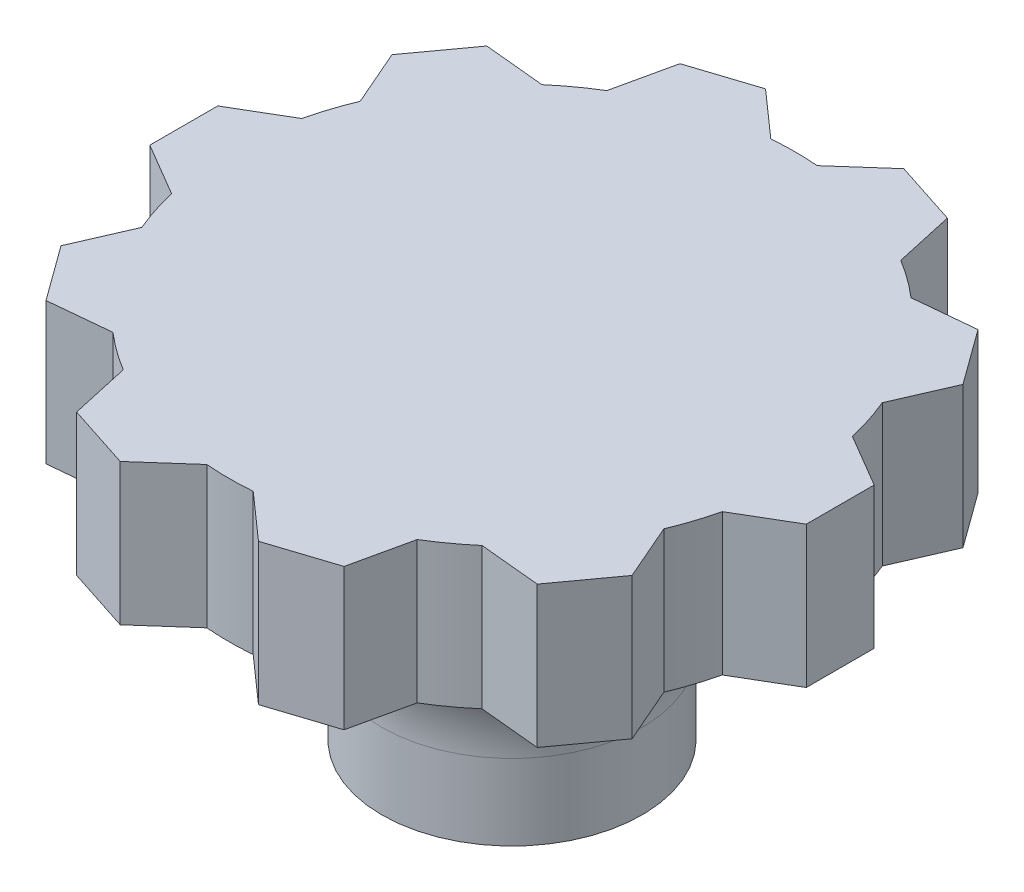
SolidWorks part; units mm, degrees
ref_plane "Front Plane" through (0, 0, 0) normal (0, 0, 1) x (1, 0, 0)
ref_plane "Top Plane" through (0, 0, 0) normal (0, 1, 0) x (1, 0, 0)
ref_plane "Right Plane" through (0, 0, 0) normal (1, 0, 0) x (0, 0, -1)
sketch "Sketch1" plane through (0, 0, 0) normal (0, 1, 0) x (1, 0, 0)
  circle A0 centre (0, 0) radius 11.5
extrude "Boss-Extrude1" add sketch "Sketch1" along normal blind 20
sketch "Sketch2" plane through (0, 20, 0) normal (0, 1, 0) x (1, 0, 0)
  line L1 (29, 0) -> (29, 3)
  line L2 (29, 0) -> (29, -3)
  line L5 (29, 3) -> (24.33, 5.7489)
  line L6 (29, -3) -> (24.33, -5.7489)
  line L9 (25.2248, -14.6187) -> (23.0625, -9.6498)
  line L10 (23.4615, -17.0458) -> (25.2248, -14.6187)
  line L11 (23.4615, -17.0458) -> (21.6981, -19.4728)
  line L12 (21.6981, -19.4728) -> (16.3043, -18.9518)
  line L15 (11.8147, -26.6536) -> (12.986, -21.3627)
  line L16 (8.9615, -27.5806) -> (11.8147, -26.6536)
  line L17 (8.9615, -27.5806) -> (6.1083, -28.5077)
  line L18 (6.1083, -28.5077) -> (2.0508, -24.9157)
  line L21 (-6.1083, -28.5077) -> (-2.0508, -24.9157)
  line L22 (-8.9615, -27.5806) -> (-6.1083, -28.5077)
  line L23 (-8.9615, -27.5806) -> (-11.8147, -26.6536)
  line L24 (-11.8147, -26.6536) -> (-12.986, -21.3627)
  line L27 (-21.6981, -19.4728) -> (-16.3043, -18.9518)
  line L28 (-23.4615, -17.0458) -> (-21.6981, -19.4728)
  line L29 (-23.4615, -17.0458) -> (-25.2248, -14.6187)
  line L30 (-25.2248, -14.6187) -> (-23.0625, -9.6498)
  line L33 (-29, -3) -> (-24.33, -5.7489)
  line L34 (-29, 0) -> (-29, -3)
  line L35 (-29, 0) -> (-29, 3)
  line L36 (-29, 3) -> (-24.33, 5.7489)
  line L39 (-25.2248, 14.6187) -> (-23.0625, 9.6498)
  line L40 (-23.4615, 17.0458) -> (-25.2248, 14.6187)
  line L41 (-23.4615, 17.0458) -> (-21.6981, 19.4728)
  line L42 (-21.6981, 19.4728) -> (-16.3043, 18.9518)
  line L45 (-11.8147, 26.6536) -> (-12.986, 21.3627)
  line L46 (-8.9615, 27.5806) -> (-11.8147, 26.6536)
  line L47 (-8.9615, 27.5806) -> (-6.1083, 28.5077)
  line L48 (-6.1083, 28.5077) -> (-2.0508, 24.9157)
  line L51 (6.1083, 28.5077) -> (2.0508, 24.9157)
  line L52 (8.9615, 27.5806) -> (6.1083, 28.5077)
  line L53 (8.9615, 27.5806) -> (11.8147, 26.6536)
  line L54 (11.8147, 26.6536) -> (12.986, 21.3627)
  line L57 (21.6981, 19.4728) -> (16.3043, 18.9518)
  line L58 (23.4615, 17.0458) -> (21.6981, 19.4728)
  line L59 (23.4615, 17.0458) -> (25.2248, 14.6187)
  line L60 (25.2248, 14.6187) -> (23.0625, 9.6498)
  arc A0 (24.33, 5.7489) -> (23.0625, 9.6498) centre (0, 0) ccw
  arc A1 (16.3043, 18.9518) -> (12.986, 21.3627) centre (0, 0) ccw
  arc A2 (2.0508, 24.9157) -> (-2.0508, 24.9157) centre (0, 0) ccw
  arc A3 (-12.986, 21.3627) -> (-16.3043, 18.9518) centre (0, 0) ccw
  arc A4 (-23.0625, 9.6498) -> (-24.33, 5.7489) centre (0, 0) ccw
  arc A5 (-24.33, -5.7489) -> (-23.0625, -9.6498) centre (0, 0) ccw
  arc A6 (-16.3043, -18.9518) -> (-12.986, -21.3627) centre (0, 0) ccw
  arc A7 (-2.0508, -24.9157) -> (2.0508, -24.9157) centre (0, 0) ccw
  arc A8 (12.986, -21.3627) -> (16.3043, -18.9518) centre (0, 0) ccw
  arc A9 (23.0625, -9.6498) -> (24.33, -5.7489) centre (0, 0) ccw
  point P66 (0, 0)
  dimension "D1" = 10
extrude "Boss-Extrude2" add sketch "Sketch2" along normal blind 12.5
sketch "Sketch3" plane through (0, 0, 0) normal (0, -1, 0) x (1, 0, 0)
  line L1 (2.2, 2.0396) -> (2.2, -2.0396)
  arc A0 (2.2, 2.0396) -> (2.2, -2.0396) centre (0, 0) ccw
extrude "Cut-Extrude2" cut sketch "Sketch3" against normal blind 19
ref_plane "Plane1" through (0, -10, 0) normal (0, -1, 0) x (-1, 0, 0)
sketch "Sketch5" plane through (0, -10, 0) normal (0, -1, 0) x (-1, 0, 0)
  circle A0 centre (0, 0) radius 3
extrude "Cut-Extrude3" cut sketch "Sketch5" against normal blind 17.5
fillet "Fillet1" radius 2.5 1 edges at (2.2, 7.5, 0)
fillet "Fillet3" radius 13.3 1 edges at (0, 20, 11.5)
